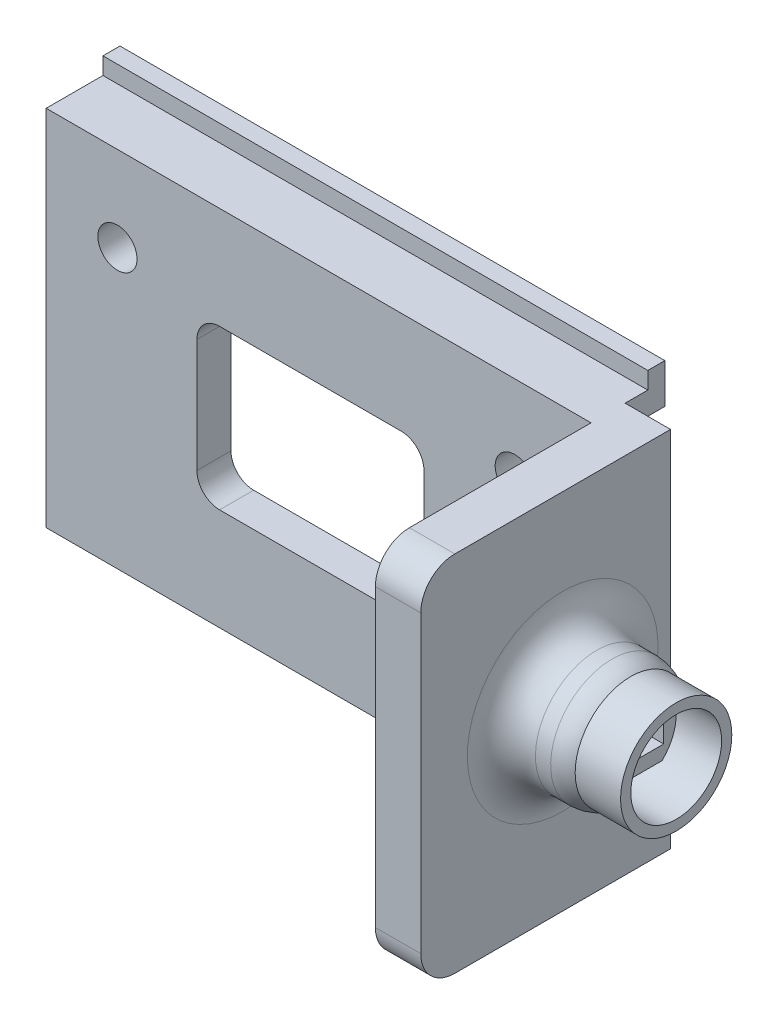
SolidWorks part; units mm, degrees
ref_plane "Front Plane" through (0, 0, 0) normal (0, 0, 1) x (1, 0, 0)
ref_plane "Top Plane" through (0, 0, 0) normal (0, 1, 0) x (1, 0, 0)
ref_plane "Right Plane" through (0, 0, 0) normal (1, 0, 0) x (0, 0, -1)
sketch "Sketch1" plane through (0, 0, 0) normal (0, 0, 1) x (1, 0, 0)
  line L1 (0, 0) -> (52, 0)
  line L2 (0, 0) -> (0, -32)
  line L3 (0, -32) -> (52, -32)
  line L4 (52, 0) -> (52, -32)
  dimension "D1" = 52
  dimension "D2" = 32
extrude "Boss-Extrude1" add sketch "Sketch1" along normal blind 3
ref_plane "Plane1" through (0, 0, 2) normal (0, 0, -1) x (-1, 0, 0)
sketch "Sketch2" plane through (0, 0, 2) normal (0, 0, -1) x (-1, 0, 0)
  line L1 (-48, 0) -> (-52, 0)
  line L2 (-48, 0) -> (-48, -32)
  line L3 (-48, -32) -> (-52, -32)
  line L4 (-52, 0) -> (-52, -32)
  dimension "D1" = 4
extrude "Boss-Extrude2" add sketch "Sketch2" against normal blind 20
fillet "Fillet1" radius 3 2 edges at (50, -32, 22) (50, 0, 22)
sketch "Sketch4" plane through (0, 0, 3) normal (0, 0, 1) x (1, 0, 0)
  line L0 (48, 0) -> (0, 0) construction
  circle A0 centre (41.2777, -7.5) radius 1.725
  circle A1 centre (6.2777, -7.5) radius 1.725
  dimension "D1" = 35
  dimension "D2" = 7.5
  dimension "D3" = 7.5
extrude "Cut-Extrude2" cut sketch "Sketch4" against normal up to surface (3 mm away) up to face at (26, -16, 0)
sketch "Sketch6" plane through (0, 0, 3) normal (0, 0, 1) x (1, 0, 0)
  line L0 (48, 0) -> (0, 0) construction
  line L1 (33.2777, -9) -> (13.2777, -9)
  line L2 (33.2777, -9) -> (33.2777, -23)
  line L3 (33.2777, -23) -> (13.2777, -23)
  line L4 (13.2777, -9) -> (13.2777, -23)
  circle A0 centre (6.2777, -7.5) radius 1.725 construction
  dimension "D3" = 7
  dimension "D1" = 14
  dimension "D2" = 20
  dimension "D4" = 9
extrude "Cut-Extrude3" cut sketch "Sketch6" against normal up to surface (3 mm away) up to face at (43.0027, -7.5, 0)
sketch "Sketch7" plane through (52, 0, 0) normal (1, 0, 0) x (0, 0, -1)
  line L0 (-22, -16) -> (2.0181, -16) construction
  line L1 (-12.4, -17.7) -> (-6.6, -17.7)
  line L2 (-12.4, -17.7) -> (-12.4, -14.3)
  line L3 (-12.4, -14.3) -> (-6.6, -14.3)
  line L4 (-6.6, -17.7) -> (-6.6, -14.3)
  line L5 (-22, -3) -> (-22, -29) construction
  line L6 (-9.5, -32) -> (-9.5, 5.4647) construction
  line L7 (-19, -32) -> (0, -32) construction
  line L8 (-13.6, -13.1) -> (-5.4, -13.1)
  line L9 (-5.4, -18.9) -> (-5.4, -13.1)
  line L10 (-13.6, -18.9) -> (-5.4, -18.9)
  line L11 (-13.6, -18.9) -> (-13.6, -13.1)
  dimension "D5" = 1.2
  dimension "D1" = 5.8
  dimension "D2" = 3.4
  dimension "D3" = 1.7
  dimension "D4" = 2.9
sketch "Sketch8" plane through (52, 0, 0) normal (1, 0, 0) x (0, 0, -1)
  line L0 (-9.5, -16) -> (-9.5, 10.2333) construction
  line L1 (-22, -16) -> (3, -16) construction
  line L3 (0, -32) -> (0, 0) construction
  line L6 (-19, -32) -> (0, -32) construction
  circle A0 centre (-9.5, -16) radius 4.25
  circle A1 centre (-9.5, -16) radius 5.4
  dimension "D1" = 10.8
  dimension "D2" = 8.5
  dimension "D3" = 9.5
  dimension "D4" = 16
extrude "Boss-Extrude4" add sketch "Sketch7" along normal blind 6
sketch "Sketch10" plane through (52, 0, 0) normal (1, 0, 0) x (0, 0, -1)
  line L0 (-19, -32) -> (0, -32) construction
  line L1 (0, -32) -> (0, 0) construction
  circle A0 centre (-9.5, -16) radius 4
  circle A1 centre (-9.5, -16) radius 4.9
  dimension "D1" = 9.8
  dimension "D2" = 8
  dimension "D3" = 16
  dimension "D4" = 9.5
extrude "Boss-Extrude6" add sketch "Sketch10" along normal blind 10
extrude "Boss-Extrude5" add sketch "Sketch8" along normal blind 6
fillet "Fillet2" radius 2 4 edges at (13.2777, -9, 1.5) (13.2777, -23, 1.5) (33.2777, -9, 1.5) (33.2777, -23, 1.5)
fillet "Fillet3" radius 3 2 edges at (52, -21.4, 9.5) (58, -16, 4.1)
sketch "Sketch15" plane through (0, 0, 0) normal (-1, 0, 0) x (0, 0, 1)
  line L1 (3, -32) -> (0, -32) construction
  line L6 (-3.5, -2) -> (-3.5, 1.5)
  line L8 (0, -16) -> (-8.2188, -16) construction
  line L9 (0, 0) -> (0, -32) construction
  line L17 (0, -2) -> (-3.5, -2)
  line L23 (-3.5, -33.5) -> (-2, -33.5)
  line L24 (-3.5, -30) -> (-3.5, -33.5)
  line L25 (0, -30) -> (-3.5, -30)
  line L26 (0, -32) -> (0, -30)
  line L27 (-2, -32) -> (0, -32)
  line L28 (-2, -33.5) -> (-2, -32)
  line L29 (0, 0) -> (0, -2)
  line L30 (-2, 0) -> (0, 0)
  line L31 (-2, 1.5) -> (-2, 0)
  line L32 (-3.5, 1.5) -> (-2, 1.5)
  dimension "D1" = 2
  dimension "D2" = 2
  dimension "D3" = 3.5
extrude "Boss-Extrude7" add sketch "Sketch15" against normal up to surface (48 mm away) up to face at (48, -16, 14.8738)
sketch "Sketch16" plane through (0, 0, 2) normal (0, 0, -1) x (-1, 0, 0)
  line L0 (0, -16) -> (-52, -16) construction
  line L1 (0, -2) -> (0, -30) construction
  line L2 (-52, -32) -> (-52, 0) construction
  line L3 (-26, -16) -> (-26, 2.5712) construction
